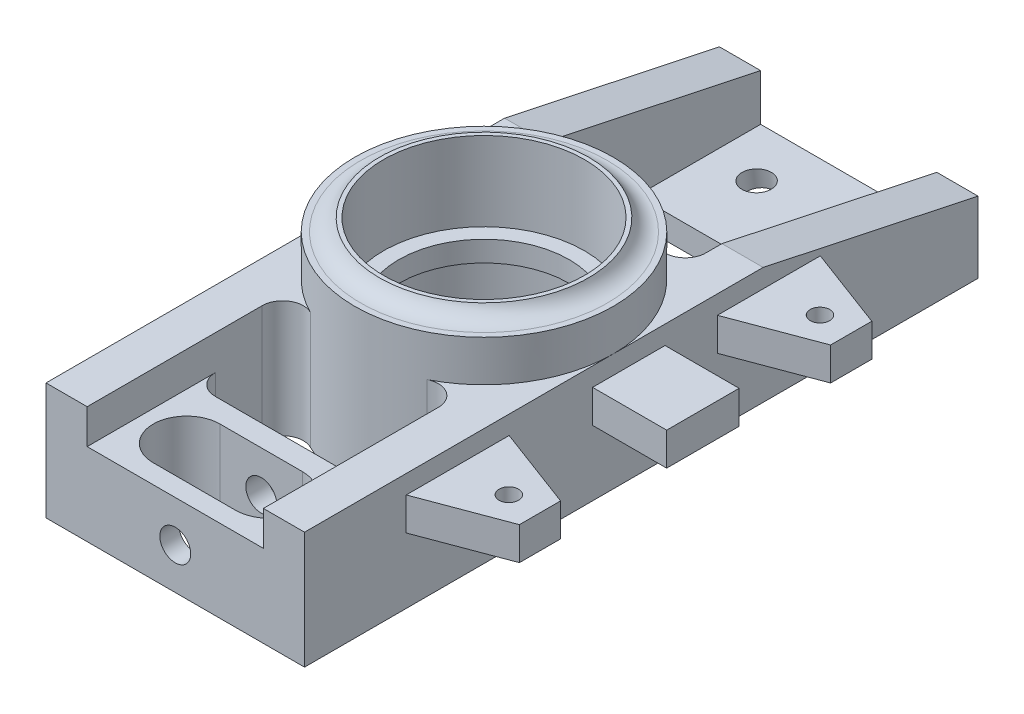
SolidWorks part; units mm, degrees
material "6061-T6 (SS)"
ref_plane "Front Plane" through (0, 0, 0) normal (0, 0, 1) x (1, 0, 0)
ref_plane "Top Plane" through (0, 0, 0) normal (0, 1, 0) x (1, 0, 0)
ref_plane "Right Plane" through (0, 0, 0) normal (1, 0, 0) x (0, 0, -1)
sketch "Bearing Sketch" plane through (0, 0, 0) normal (1, 0, 0) x (0, 0, -1)
  line L0 (0, 0) -> (0, 16.3466) construction
  line L1 (4.8872, 0) -> (-19.6002, 0) construction
  line L2 (-39.878, 0) -> (-39.878, 48.768)
  line L3 (-39.878, 48.768) -> (-32.258, 48.768)
  line L4 (-32.258, 48.768) -> (-32.258, 52.578)
  line L5 (-32.258, 52.578) -> (-30.9994, 52.578)
  line L6 (-30.9994, 52.578) -> (-30.9994, 28.194)
  line L7 (-30.9994, 28.194) -> (-26.289, 28.194)
  line L8 (-26.289, 28.194) -> (-26.289, 21.844)
  line L9 (-26.289, 21.844) -> (-30.9994, 21.844)
  line L10 (-30.9994, 21.844) -> (-30.9994, 0)
  line L11 (-30.9994, 0) -> (-39.878, 0)
  point P2 (-32.258, 50.673)
  dimension "D1" = 61.9989
  dimension "D2" = 61.9989
  dimension "D3" = 6.35
  dimension "D4" = 48.768
  dimension "D5" = 64.516
  dimension "D6" = 79.756
  dimension "D7" = 24.384
  dimension "D8" = 21.844
  dimension "D9" = 52.578
revolve "Bearing Revolve" add sketch "Bearing Sketch" angle 360 about L0
fillet "Housing Fillet Lip" radius 6.35 1 edges at (0, 48.768, -32.258)
sketch "PrepArea(WithadjWidth)" plane through (0, 0, 0) normal (0, 1, 0) x (1, 0, 0)
  line L2 (0, 0) -> (0, 15.1173) construction
  line L3 (-39.878, 0) -> (-39.878, 112.522)
  line L4 (-39.878, 112.522) -> (39.878, 112.522)
  line L5 (39.878, 112.522) -> (39.878, 0)
  circle A2 centre (0, 0) radius 39.878 construction
  arc A3 (-39.878, 0) -> (39.878, 0) centre (0, 0) cw
  dimension "D2" = 72.644
extrude "UBJ Material Prep" add sketch "PrepArea(WithadjWidth)" along normal offset from surface (36.068 mm away) 12.7 up to face at (0, 48.768, -38.0779)
sketch "Flat Camber Spot" plane through (0, 36.068, 0) normal (0, 1, 0) x (1, 0, 0)
  line L0 (-27.178, 112.522) -> (-27.178, 29.1824)
  line L1 (-39.878, 112.522) -> (39.878, 112.522) construction
  line L2 (27.178, 112.522) -> (27.178, 29.1824)
  line L3 (-39.878, 0) -> (-39.878, 112.522) construction
  line L4 (39.878, 112.522) -> (39.878, 0) construction
  line L5 (-27.178, 112.522) -> (27.178, 112.522)
  arc A0 (39.878, 0) -> (-39.878, 0) centre (0, 0) ccw construction
  arc A1 (-27.178, 29.1824) -> (27.178, 29.1824) centre (0, 0) cw
  circle A2 centre (0, 0) radius 39.878 construction
  dimension "D1" = 12.7
  dimension "D2" = 12.7
extrude "UBJ Flat Camber Spot" cut sketch "Flat Camber Spot" against normal offset from surface (28.448 mm away) 7.62
sketch "WeightUpper Cut " plane through (0, 7.62, 0) normal (0, 1, 0) x (1, 0, 0)
  line L0 (-27.178, 74.422) -> (27.178, 74.422)
  line L1 (-27.178, 112.522) -> (-27.178, 29.1824) construction
  line L2 (27.178, 112.522) -> (27.178, 29.1824) construction
  line L3 (27.178, 74.422) -> (27.178, 29.1824)
  line L4 (-27.178, 74.422) -> (-27.178, 29.1824)
  line L5 (-27.178, 112.522) -> (27.178, 112.522) construction
  arc A0 (-27.178, 29.1824) -> (-39.878, 0) centre (0, 0) ccw construction
  arc A1 (-27.178, 29.1824) -> (27.178, 29.1824) centre (0, 0) cw
  arc A2 (27.178, 29.1824) -> (-27.178, 29.1824) centre (0, 0) ccw construction
  dimension "D1" = 38.1
extrude "Weight Saving Upper Cut" cut sketch "WeightUpper Cut " against normal up to surface (7.62 mm away)
sketch "Sketch8" plane through (-39.878, 0, 0) normal (-1, 0, 0) x (0, 0, 1)
  line L0 (-112.522, 21.9768) -> (-46.228, 36.068)
  line L1 (-112.522, 36.068) -> (-112.522, 0) construction
  line L2 (0, 36.068) -> (-112.522, 36.068) construction
  line L3 (-46.228, 36.068) -> (-112.522, 36.068)
  line L4 (-112.522, 36.068) -> (-112.522, 21.9768)
  line L5 (-39.878, 48.768) -> (-39.878, 0) construction
  dimension "D1" = 6.35
  dimension "D2" = 12
extrude "Weight Save Arm Short" cut sketch "Sketch8" against normal up to surface (79.756 mm away) up to face at (39.878, 18.034, -56.261)
fillet "UBJ Fillet " radius 6.35 6 edges at (27.178, 3.81, -74.422) (-27.178, 3.81, -74.422) (-27.178, 18.034, -29.1824) (27.178, 18.034, -29.1824) (39.878, 18.034, 0) (-39.878, 18.034, 0)
ref_plane "UBJ Hole Angle Plane" through (0, -15.8185, -2.2696) normal (0, -0.9899, -0.142) x (-1, 0, 0)
sketch "UBJ Hole Sketch" plane through (0, -15.8185, -2.2696) normal (0, -0.9899, -0.142) x (-1, 0, 0)
  line L0 (0, 111.3814) -> (0, 96.1046) construction
  line L2 (-39.878, 111.3814) -> (39.878, 111.3814) construction
  circle A0 centre (-12.7, 96.9034) radius 4.5
  circle A2 centre (12.7, 96.9034) radius 4.5
  point P5 (-24.5687, 87.5729)
  point P6 (-15.0131, 96.1046)
  dimension "D1" = 9
  dimension "D2" = 25.4
  dimension "D3" = 14.478
extrude "UBJ Holes" cut sketch "UBJ Hole Sketch" against normal up to surface (9.1296 mm away) up to face at (0, 7.62, -85.4437)
sketch "Sketch18" plane through (0, -15.8185, -2.2696) normal (0, -0.9899, -0.142) x (-1, 0, 0)
  circle A0 centre (-12.7, 96.9034) radius 8
  circle A1 centre (12.7, 96.9034) radius 8
  dimension "D1" = 16
  dimension "D2" = 16
extrude "Cut-Extrude2" cut sketch "Sketch18" against normal blind 3.81
sketch "Sketch9" plane through (0, 0, 0) normal (0, -1, 0) x (1, 0, 0)
  line L0 (-39.878, 0) -> (-39.878, 95.25)
  line L1 (-39.878, 95.25) -> (39.878, 95.25)
  line L2 (39.878, 95.25) -> (39.878, 0)
  line L3 (-39.878, -112.522) -> (-39.878, 0) construction
  arc A2 (39.878, 0) -> (-39.878, 0) centre (0, 0) ccw construction
  arc A3 (-39.878, 0) -> (39.878, 0) centre (0, 0) cw
  dimension "D1" = 95.25
extrude "LBJ Material Prep" add sketch "Sketch9" against normal offset from surface (36.068 mm away) 12.7 up to face at (0, 48.768, -38.0779)
sketch "Sketch10" plane through (0, 36.068, 0) normal (0, 1, 0) x (1, 0, 0)
  line L0 (-27.178, -29.1824) -> (-27.178, -95.25)
  line L1 (-39.878, -95.25) -> (39.878, -95.25) construction
  line L2 (27.178, -29.1824) -> (27.178, -95.25)
  line L3 (-39.878, 0) -> (-39.878, -95.25) construction
  line L4 (39.878, -95.25) -> (39.878, 0) construction
  line L5 (-27.178, -95.25) -> (27.178, -95.25)
  circle A0 centre (0, 0) radius 39.878 construction
  arc A1 (-27.178, -29.1824) -> (27.178, -29.1824) centre (0, 0) ccw
  dimension "D1" = 12.7
  dimension "D2" = 12.7
extrude "Flat LBJ Prep" cut sketch "Sketch10" against normal offset from surface (10.668 mm away) 25.4 up to face at (12.7, 0, -105.9777)
sketch "Sketch12" plane through (0, 25.4, 0) normal (0, 1, 0) x (1, 0, 0)
  line L0 (-12.7, -79.0429) -> (12.7, -79.0429) construction
  line L1 (-12.7, -68.7178) -> (12.7, -68.7178)
  line L2 (-12.7, -89.368) -> (12.7, -89.368)
  line L3 (27.178, -95.25) -> (-27.178, -95.25) construction
  line L4 (0, 0) -> (0, -140.8541) construction
  arc A0 (-12.7, -68.7178) -> (-12.7, -89.368) centre (-12.7, -79.0429) ccw
  arc A1 (12.7, -89.368) -> (12.7, -68.7178) centre (12.7, -79.0429) ccw
  point P2 (0, -79.0429)
  dimension "D1" = 20.6502
  dimension "D2" = 25.4
  dimension "D3" = 5.882
extrude "LBJ Slot" cut sketch "Sketch12" against normal up to surface (25.4 mm away) up to face at (12.7, 0, -105.9777)
sketch "Sketch13" plane through (0, 25.4, 0) normal (0, 1, 0) x (1, 0, 0)
  line L0 (-27.178, -29.1824) -> (-27.178, -62.0757)
  line L1 (-27.178, -95.25) -> (-27.178, -29.1824) construction
  line L2 (-27.178, -62.0757) -> (27.178, -62.0757)
  line L3 (27.178, -29.1824) -> (27.178, -95.25) construction
  line L4 (27.178, -62.0757) -> (27.178, -29.1824)
  line L5 (12.7, -68.7178) -> (-12.7, -68.7178) construction
  arc A0 (-27.178, -29.1824) -> (27.178, -29.1824) centre (0, 0) ccw
  circle A1 centre (0, 0) radius 39.878 construction
  dimension "D1" = 6.6421
extrude "LBJ Weight and Bolt Clearing" cut sketch "Sketch13" against normal up to surface (25.4 mm away) up to face at (0, 0, 79.0429)
fillet "LBJ Fillet" radius 6.35 4 edges at (27.178, 12.7, 62.0757) (-27.178, 12.7, 62.0757) (27.178, 18.034, 29.1824) (-27.178, 18.034, 29.1824)
sketch "Sketch14" plane through (0, 0, 95.25) normal (0, 0, 1) x (1, 0, 0)
  line L2 (0, 0) -> (0, 25.4) construction
  line L3 (27.178, 25.4) -> (-27.178, 25.4) construction
  circle A0 centre (0, 12.7) radius 4.7625
  dimension "D1" = 9.525
extrude "LBJ Hole" cut sketch "Sketch14" against normal up to surface (33.1743 mm away) up to face at (0, 12.7, 62.0757)
ref_plane "Brake Caliper Face" through (0, 20.17, 0) normal (0, -1, 0) x (-1, 0, 0)
sketch "Brake Holer" plane through (0, 20.17, 0) normal (0, -1, 0) x (-1, 0, 0)
  line L0 (0, 0) -> (-102.3281, 0) construction
  line L1 (-55.6468, 96.4315) -> (-55.6468, -50.9955) construction
  line L2 (-39.878, -32.125) -> (-65.278, -41.65)
  line L3 (-39.878, -95.25) -> (-39.878, 112.522) construction
  line L4 (-65.278, -41.65) -> (-65.278, -54.35)
  line L5 (-65.278, -54.35) -> (-39.878, -63.875)
  line L6 (-39.878, -32.125) -> (-39.878, -63.875)
  line L7 (-39.878, 32.125) -> (-39.878, 63.875)
  line L8 (-65.278, 54.35) -> (-39.878, 63.875)
  line L9 (-65.278, 41.65) -> (-65.278, 54.35)
  line L10 (-39.878, 32.125) -> (-65.278, 41.65)
  circle A0 centre (-55.6468, 48) radius 3
  circle A1 centre (-55.6468, -48) radius 3
  dimension "D3" = 6
  dimension "D4" = 6
  dimension "D1" = 96
  dimension "D2" = 55.6468
  dimension "D5" = 25.4
  dimension "D6" = 6.35
  dimension "D7" = 31.75
  dimension "D8" = 12.7
  dimension "D9" = 48
extrude "Brake Caliper Holer" add sketch "Brake Holer" against normal blind 10.16
sketch "Sketch16" plane through (0, 20.17, 0) normal (0, -1, 0) x (-1, 0, 0)
  line L0 (9.3649, 4.7914) -> (-72.4402, 4.7914) construction
  line L2 (-62.738, -6.3846) -> (-39.878, -6.3846)
  line L3 (-62.738, -6.3846) -> (-62.738, 15.9674)
  line L4 (-62.738, 15.9674) -> (-39.878, 15.9674)
  line L5 (-39.878, -6.3846) -> (-39.878, 15.9674)
  line L6 (-62.738, -6.3846) -> (-39.878, 15.9674) construction
  line L7 (-62.738, 15.9674) -> (-39.878, -6.3846) construction
  line L9 (-39.878, -95.25) -> (-39.878, 112.522) construction
  point P1 (-51.308, 4.7914)
  dimension "D1" = 22.86
  dimension "D2" = 22.352
extrude "Speed Sensor Extrude" add sketch "Sketch16" against normal blind 10.16
sketch "Sketch19" plane through (-39.878, 0, 0) normal (-1, 0, 0) x (0, 0, 1)
  circle A0 centre (31.2928, 26.67) radius 1.27
  circle A1 centre (31.2928, 9.525) radius 1.27
  circle A2 centre (55.1053, 9.525) radius 1.27
  point P0 (31.2928, 9.525)
  point P1 (31.2928, 26.67)
  point P2 (55.1053, 9.525)
  point P10 (0, 0)
  dimension "D5" = 2.54
  dimension "D6" = 2.54
  dimension "D7" = 2.54
  dimension "D1" = 17.145
  dimension "D2" = 23.8125
  dimension "D3" = 9.525
  dimension "D4" = 31.2928
extrude "Toe Brakcet Holes" cut sketch "Sketch19" against normal blind 9
thread "Thread1" pitch 0.7937 method cut profile "Thread Profile1" start angle 0, offset 0, length 10, pitch 0.7937, diameter 2.54
ref_plane "Plane2" through (-39.878, 26.67, 30.0228) normal (0, -1, 0) x (0, 0, -1)
sketch "Thread Profile1" plane through (-39.878, 26.67, 30.0228) normal (0, -1, 0) x (0, 0, -1)
  line L0 (0, 0) -> (0, 0.7937) construction
  line L1 (0, 0) -> (0.4296, 0.248)
  line L2 (0.4296, 0.248) -> (0.4296, 0.3473)
  line L3 (0.4296, 0.3473) -> (0, 0.5953)
  line L4 (0.4296, 0.2977) -> (0, 0.2977) construction
  line L11 (0, 0) -> (0, 0.5953)
  point P2 (0, 0)
  dimension "Pitch" = 0.7937
  dimension "Profile_Angle" = 60
  dimension "Profile_Land" = 0.0992
  dimension "Profile_Height" = 0.4296
thread "Thread2" pitch 0.7937 method cut profile "Thread Profile2" start angle 0, offset 0, length 10, pitch 0.7937, diameter 2.54
ref_plane "Plane3" through (-39.878, 9.525, 30.0228) normal (0, -1, 0) x (0, 0, -1)
sketch "Thread Profile2" plane through (-39.878, 9.525, 30.0228) normal (0, -1, 0) x (0, 0, -1)
  line L0 (0, 0) -> (0, 0.7937) construction
  line L1 (0, 0) -> (0.4296, 0.248)
  line L2 (0.4296, 0.248) -> (0.4296, 0.3473)
  line L3 (0.4296, 0.3473) -> (0, 0.5953)
  line L4 (0.4296, 0.2977) -> (0, 0.2977) construction
  line L11 (0, 0) -> (0, 0.5953)
  point P2 (0, 0)
  dimension "Pitch" = 0.7937
  dimension "Profile_Angle" = 60
  dimension "Profile_Land" = 0.0992
  dimension "Profile_Height" = 0.4296
thread "Thread3" pitch 0.7937 method cut profile "Thread Profile3" start angle 0, offset 0, length 10, pitch 0.7937, diameter 2.54
ref_plane "Plane4" through (-39.878, 9.525, 53.8353) normal (0, -1, 0) x (0, 0, -1)
sketch "Thread Profile3" plane through (-39.878, 9.525, 53.8353) normal (0, -1, 0) x (0, 0, -1)
  line L0 (0, 0) -> (0, 0.7937) construction
  line L1 (0, 0) -> (0.4296, 0.248)
  line L2 (0.4296, 0.248) -> (0.4296, 0.3473)
  line L3 (0.4296, 0.3473) -> (0, 0.5953)
  line L4 (0.4296, 0.2977) -> (0, 0.2977) construction
  line L11 (0, 0) -> (0, 0.5953)
  point P2 (0, 0)
  dimension "Pitch" = 0.7937
  dimension "Profile_Angle" = 60
  dimension "Profile_Land" = 0.0992
  dimension "Profile_Height" = 0.4296
equation "\"KPI\"= 9.8deg"
equation "\"Bearing_Inner_Boar\"= 1.25in"
equation "\"Bearing_Outer_Bore\"= 2.4409in'TK, This is for press fit check again."
equation "\"Bearing_Thickness\"= .7150in"
equation "\"D1@Bearing Sketch\"=\"Bearing_Outer_Bore\""
equation "\"D2@Bearing Sketch\"=\"Bearing_Outer_Bore\""
equation "\"D2@PrepArea(WithadjWidth)\"=.25+2.61"
equation "\"Vert_LBJ\"= 3.2in"
equation "\"D1@Sketch9\"=\"Vert_LBJ\"+.25+.3"
